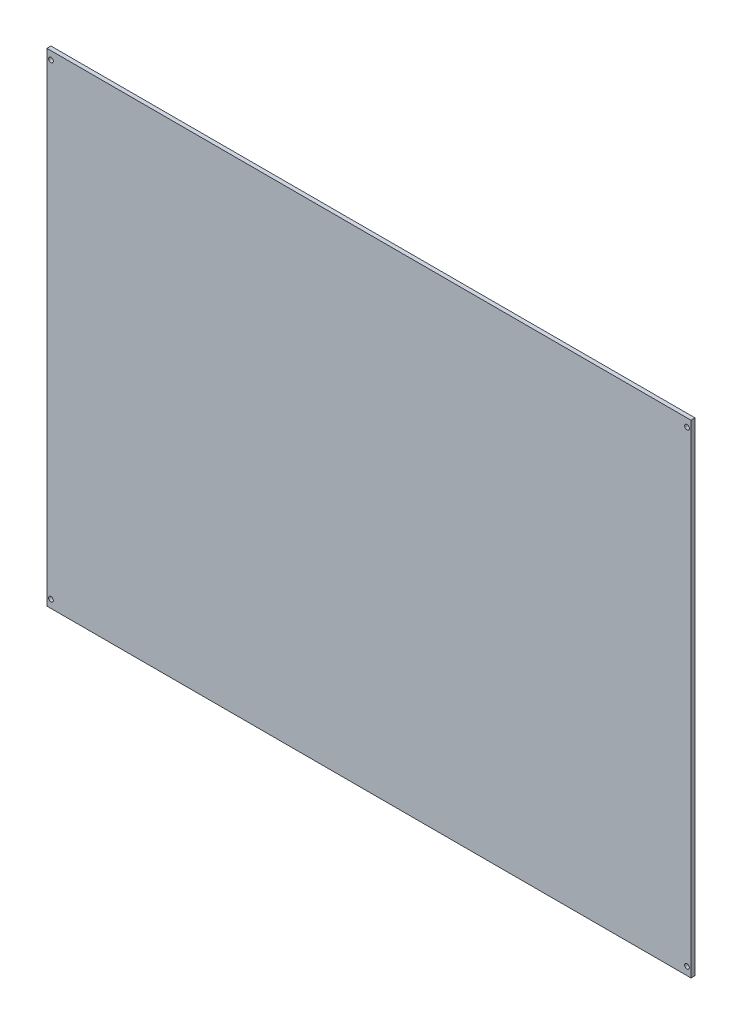
SolidWorks part; units mm, degrees
ref_plane "Front Plane" through (0, 0, 0) normal (0, 0, 1) x (1, 0, 0)
ref_plane "Top Plane" through (0, 0, 0) normal (0, 1, 0) x (1, 0, 0)
ref_plane "Right Plane" through (0, 0, 0) normal (1, 0, 0) x (0, 0, -1)
sketch "Sketch1" plane through (0, 0, 0) normal (0, 0, 1) x (1, 0, 0)
  line L1 (-254, -190.5) -> (254, -190.5)
  line L2 (-254, -190.5) -> (-254, 190.5)
  line L3 (-254, 190.5) -> (254, 190.5)
  line L4 (254, -190.5) -> (254, 190.5)
  line L5 (-254, -190.5) -> (254, 190.5) construction
  line L6 (-254, 190.5) -> (254, -190.5) construction
  point P0 (0, 0)
  dimension "D1" = 508
  dimension "D2" = 381
extrude "Boss-Extrude1" add sketch "Sketch1" along normal blind 3.175
sketch "Sketch2" plane through (0, 0, 3.175) normal (0, 0, 1) x (1, 0, 0)
  line L0 (-250.825, 190.5) -> (-250.825, -190.5) construction
  line L1 (254, 190.5) -> (-254, 190.5) construction
  line L2 (-254, -190.5) -> (254, -190.5) construction
  line L3 (250.825, 190.5) -> (250.825, -190.5) construction
  line L4 (254, -190.5) -> (254, 190.5) construction
  line L5 (-254, 190.5) -> (-254, -190.5) construction
  circle A0 centre (-250.825, -184.15) radius 1.8542
  circle A1 centre (-250.825, 184.15) radius 1.8542
  circle A2 centre (250.825, 184.15) radius 1.8542
  circle A3 centre (250.825, -184.15) radius 1.8542
  dimension "D3" = 3.7084
  dimension "D1" = 3.175
  dimension "D2" = 3.175
  dimension "D4" = 6.35
  dimension "D5" = 6.35
  dimension "D6" = 6.35
  dimension "D7" = 6.35
extrude "Cut-Extrude1" cut sketch "Sketch2" against normal blind 3.175
